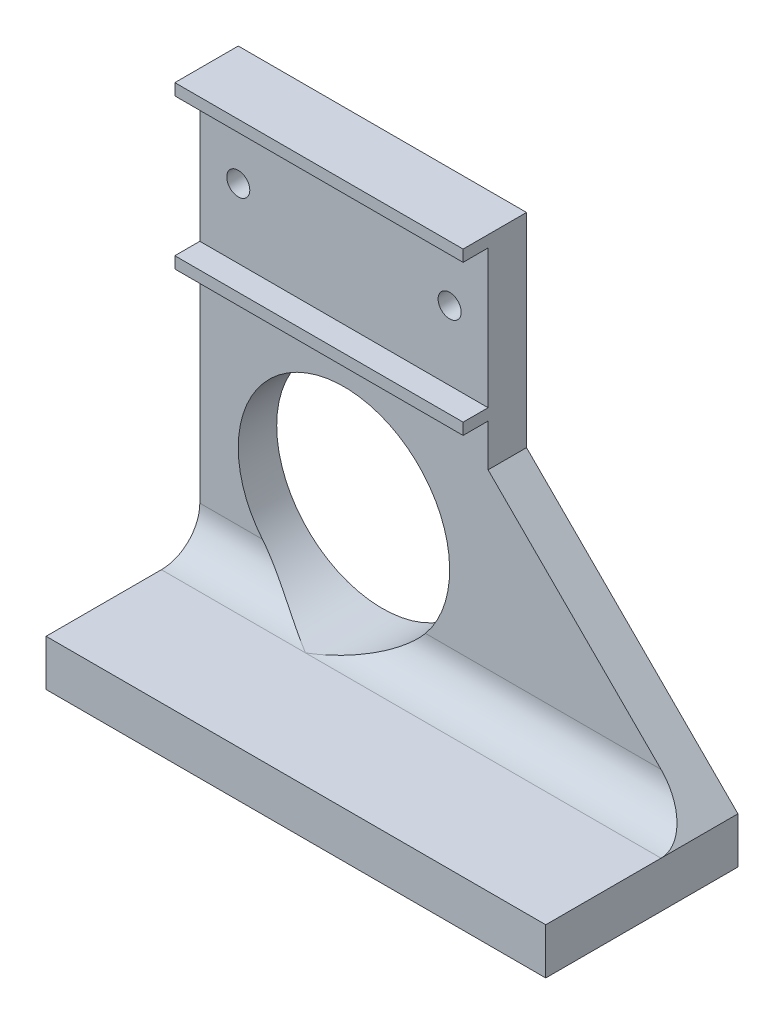
SolidWorks part; units mm, degrees
ref_plane "Front Plane" through (0, 0, 0) normal (0, 0, 1) x (1, 0, 0)
ref_plane "Top Plane" through (0, 0, 0) normal (0, 1, 0) x (1, 0, 0)
ref_plane "Right Plane" through (0, 0, 0) normal (1, 0, 0) x (0, 0, -1)
sketch "Sketch2" plane through (0, 0, 0) normal (0, 0, 1) x (1, 0, 0)
  line L0 (0, 0) -> (130, 0)
  line L1 (130, 0) -> (130, 12)
  line L2 (130, 12) -> (75, 67)
  line L3 (75, 67) -> (75, 120)
  line L4 (75, 120) -> (0, 120)
  line L5 (0, 120) -> (0, 0)
  dimension "D1" = 120
  dimension "D2" = 75
  dimension "D3" = 12
  dimension "D4" = 55
  dimension "D5" = 130
extrude "Boss-Extrude1" add sketch "Sketch2" against normal blind 10
sketch "Sketch3" plane through (0, 0, 0) normal (0, 0, 1) x (1, 0, 0)
  line L0 (75, 67) -> (75, 120) construction
  line L1 (0, 120) -> (75, 120)
  line L2 (0, 120) -> (0, 117)
  line L3 (0, 117) -> (75, 117)
  line L4 (75, 120) -> (75, 117)
  line L5 (0, 120) -> (75, 117) construction
  line L6 (0, 117) -> (75, 120) construction
  line L7 (0, 120) -> (0, 0) construction
  line L8 (0, 81) -> (75, 81)
  line L9 (0, 81) -> (0, 78)
  line L10 (0, 78) -> (75, 78)
  line L11 (75, 81) -> (75, 78)
  line L12 (0, 81) -> (75, 78) construction
  line L13 (0, 78) -> (75, 81) construction
  point P4 (37.5, 118.5)
  point P12 (37.5, 79.5)
  dimension "D1" = 3
  dimension "D2" = 36
extrude "Boss-Extrude2" add sketch "Sketch3" along normal blind 6.5
sketch "Sketch4" plane through (0, 0, 0) normal (0, 0, 1) x (1, 0, 0)
  line L0 (0, 99) -> (75, 99) construction
  line L1 (0, 117) -> (0, 81) construction
  line L2 (75, 81) -> (75, 117) construction
  circle A0 centre (10, 99) radius 3
  circle A1 centre (65, 99) radius 3
  dimension "D1" = 10
  dimension "D3" = 6
  dimension "D2" = 10
extrude "Cut-Extrude2" cut sketch "Sketch4" against normal up to surface (10 mm away) up to face at (68.3333, 53.1667, -10)
sketch "Sketch5" plane through (0, 0, 0) normal (0, 0, 1) x (1, 0, 0)
  line L1 (0, 0) -> (130, 0)
  line L2 (0, 0) -> (0, 12)
  line L3 (0, 12) -> (130, 12)
  line L4 (130, 0) -> (130, 12)
  line L5 (0, 0) -> (130, 12) construction
  line L6 (0, 12) -> (130, 0) construction
  point P4 (65, 6)
extrude "Boss-Extrude3" add sketch "Sketch5" along normal blind 40
fillet "Fillet1" radius 10 1 edges at (65, 12, 0)
sketch "Sketch6" plane through (0, 0, -10) normal (0, 0, -1) x (-1, 0, 0)
  line L0 (-37.5, 120) -> (-37.5, 0) construction
  line L1 (-75, 120) -> (0, 120) construction
  line L2 (0, 0) -> (-130, 0) construction
  line L3 (-130, 12) -> (0, 12) construction
  circle A0 centre (-37.5, 39.5) radius 27.5
  dimension "D1" = 55
extrude "Cut-Extrude3" cut sketch "Sketch6" against normal through all
